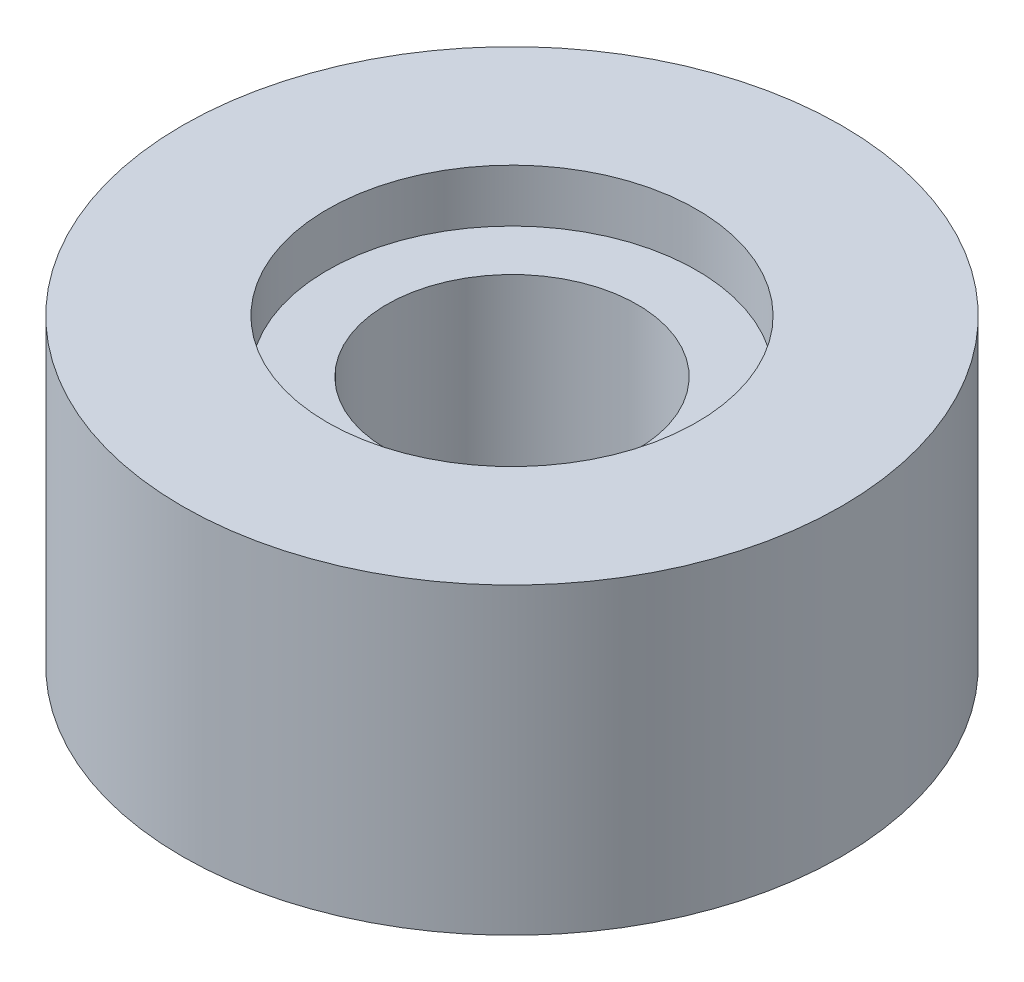
SolidWorks part; units mm, degrees
ref_plane "Front Plane" through (0, 0, 0) normal (0, 0, 1) x (1, 0, 0)
ref_plane "Top Plane" through (0, 0, 0) normal (0, 1, 0) x (1, 0, 0)
ref_plane "Right Plane" through (0, 0, 0) normal (1, 0, 0) x (0, 0, -1)
sketch "Sketch1" plane through (0, 0, 0) normal (0, 1, 0) x (1, 0, 0)
  circle A0 centre (0, 0) radius 9.5
  circle A1 centre (0, 0) radius 25
  dimension "D1" = 19
  dimension "D2" = 50
extrude "Boss-Extrude1" add sketch "Sketch1" along normal blind 15
sketch "Sketch4" plane through (0, 0, 0) normal (0, 0, 1) x (1, 0, 0)
  line L0 (-25, 7.5) -> (29.7231, 7.5) construction
  line L1 (-25, 15) -> (-25, 0) construction
sketch "Sketch2" plane through (0, 15, 0) normal (0, 1, 0) x (1, 0, 0)
  circle A0 centre (0, 0) radius 14
  circle A1 centre (0, 0) radius 25
  dimension "D1" = 28
extrude "Boss-Extrude2" add sketch "Sketch2" along normal blind 4
ref_plane "Plane1" through (0, 7.5, 0) normal (0, 1, 0) x (1, 0, 0)
mirror "Mirror1" about plane through (0, 7.5, 0) normal (0, 1, 0) of "Boss-Extrude2"
